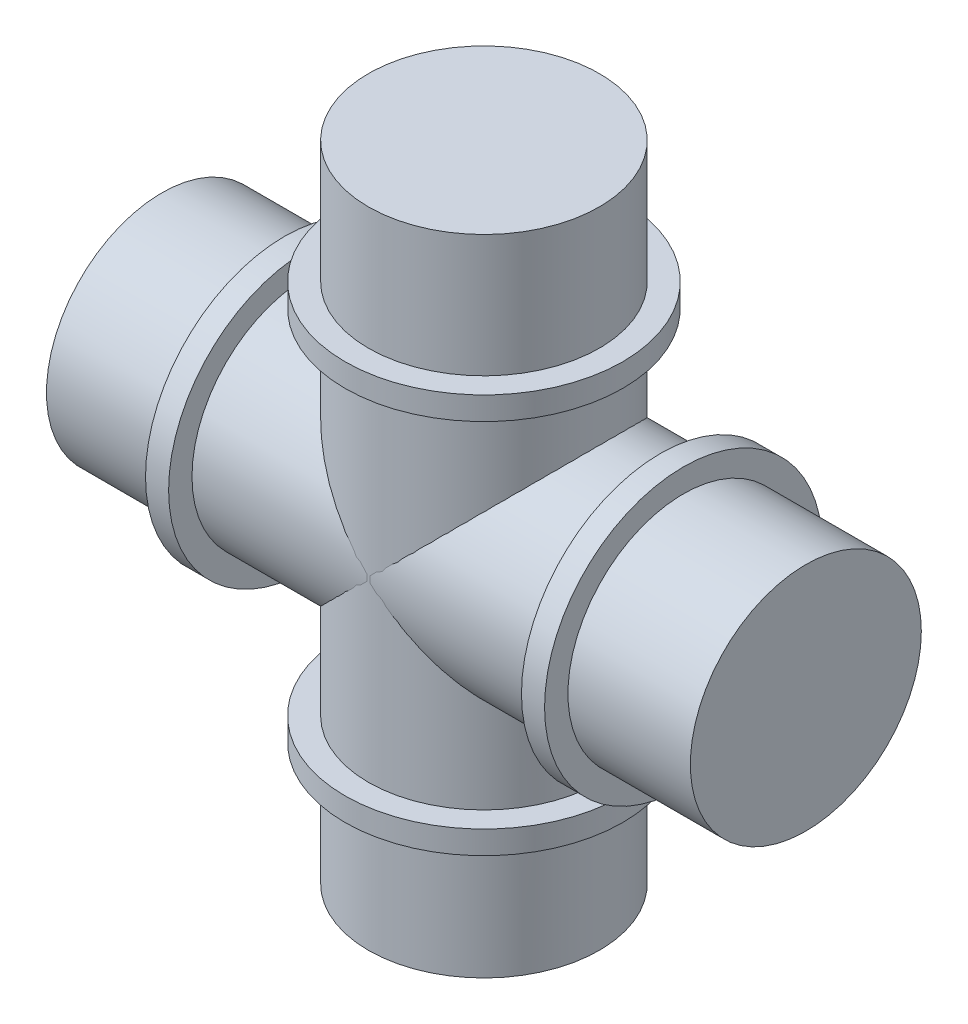
SolidWorks part; units mm, degrees
ref_plane "Front Plane" through (0, 0, 0) normal (0, 0, 1) x (1, 0, 0)
ref_plane "Top Plane" through (0, 0, 0) normal (0, 1, 0) x (1, 0, 0)
ref_plane "Right Plane" through (0, 0, 0) normal (1, 0, 0) x (0, 0, -1)
sketch "Sketch1" plane through (0, 0, 0) normal (0, 1, 0) x (1, 0, 0)
  circle A0 centre (0, 0) radius 63.5
  dimension "D1" = 127
extrude "Boss-Extrude1" add sketch "Sketch1" along normal blind 304 and the other way blind 50
sketch "Sketch3" plane through (0, 0, 0) normal (1, 0, 0) x (0, 0, -1)
  line L0 (0, 0) -> (0, 127)
  circle A0 centre (0, 127) radius 63.5
  dimension "D2" = 127
  dimension "D1" = 127
extrude "Boss-Extrude2" add sketch "Sketch3" along normal blind 177 and the other way blind 177 separate body contours A0 region at (0, 83.3687, -43.6313)
sketch "Sketch5" plane through (177, 0, 0) normal (1, 0, 0) x (0, 0, -1)
  circle A0 centre (0, 127) radius 63.5
  circle A1 centre (0, 127) radius 76.35
  dimension "D1" = 12.85
extrude "Boss-Extrude3" add sketch "Sketch5" along normal blind 12.7 from offset 80 offset against normal yes
sketch "Sketch6" plane through (0, -50, 0) normal (0, -1, 0) x (1, 0, 0)
  circle A0 centre (0, 0) radius 63.5
  circle A1 centre (0, 0) radius 76.35
  dimension "D1" = 12.85
extrude "Boss-Extrude4" add sketch "Sketch6" along normal blind 12.7 from offset 80 contours A1 offset against normal yes
sketch "Sketch7" plane through (-177, 0, 0) normal (-1, 0, 0) x (0, 0, 1)
  circle A0 centre (0, 127) radius 63.5
  circle A1 centre (0, 127) radius 76.35
  dimension "D1" = 12.85
extrude "Boss-Extrude5" add sketch "Sketch7" along normal blind 12.7 from offset 80 offset against normal yes
sketch "Sketch8" plane through (0, 304, 0) normal (0, 1, 0) x (1, 0, 0)
  circle A0 centre (0, 0) radius 63.5
  circle A1 centre (0, 0) radius 76.35
  dimension "D1" = 12.85
extrude "Boss-Extrude6" add sketch "Sketch8" along normal blind 12.7 from offset 80 contours A1 offset against normal yes
